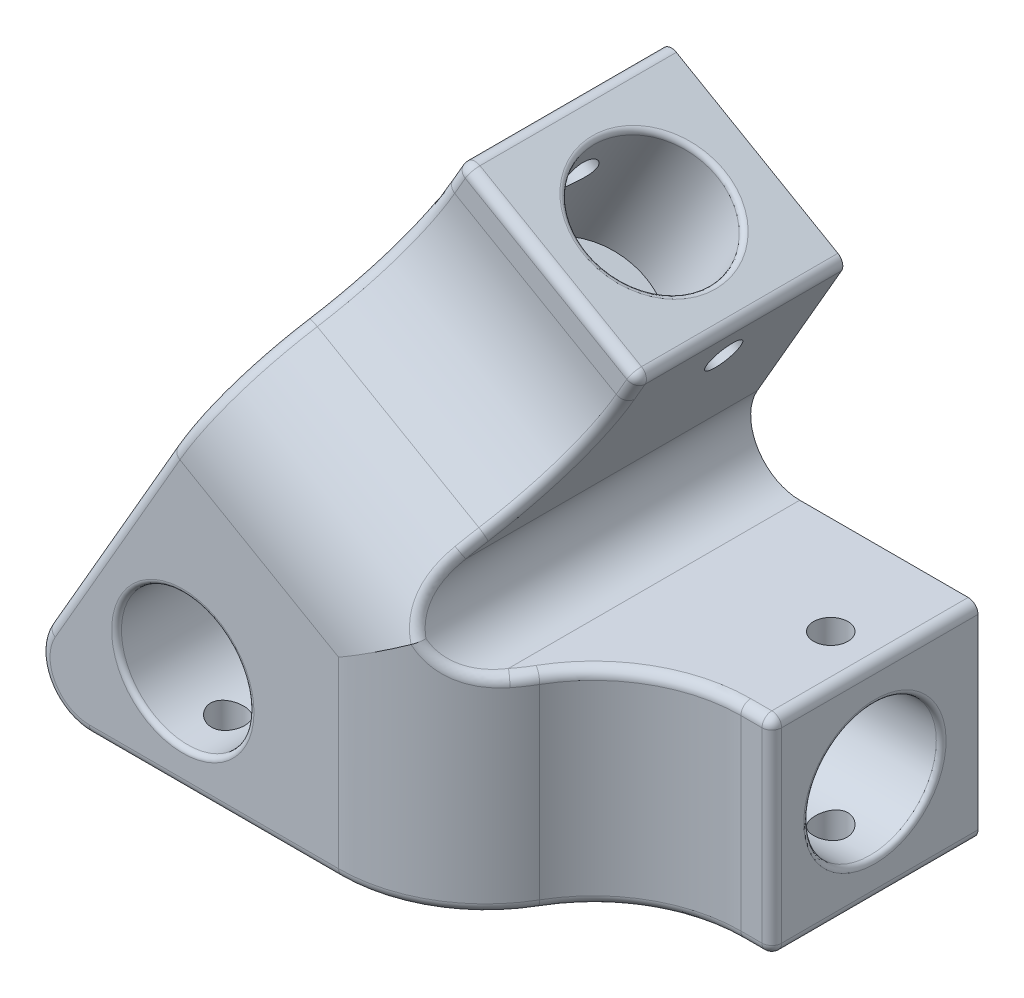
SolidWorks part; units mm, degrees
other "Corner Joint"
ref_plane "Front Plane" through (0, 0, 0) normal (0, 0, 1) x (1, 0, 0)
ref_plane "Top Plane" through (0, 0, 0) normal (0, 1, 0) x (1, 0, 0)
ref_plane "Right Plane" through (0, 0, 0) normal (1, 0, 0) x (0, 0, -1)
sketch "Sketch1" plane through (0, 0, 0) normal (0, 0, 1) x (1, 0, 0)
  line L0 (0, 0) -> (45, 0) construction
  line L1 (0, 0) -> (22.5, 38.9711) construction
  line L16 (45, -10.5) -> (-9.5263, -10.5)
  line L17 (16.8708, 42.2211) -> (28.1292, 35.7211) construction
  line L18 (16.8708, 42.2211) -> (9.3708, 29.2308) construction
  line L19 (9.3708, 29.2308) -> (20.6292, 22.7308) construction
  line L20 (28.1292, 35.7211) -> (20.6292, 22.7308) construction
  line L21 (30, 6.5) -> (45, 6.5) construction
  line L22 (30, 6.5) -> (30, -6.5) construction
  line L23 (30, -6.5) -> (45, -6.5) construction
  line L24 (45, 6.5) -> (45, -6.5) construction
  line L25 (-13.8564, -3) -> (13.4067, 44.2211)
  line L26 (13.4067, 44.2211) -> (31.5933, 33.7211)
  line L27 (31.5933, 33.7211) -> (22.5167, 18)
  line L28 (26.8468, 10.5) -> (45, 10.5)
  line L29 (45, 10.5) -> (45, -10.5)
  circle A0 centre (0, 0) radius 6.5 construction
  arc A1 (26.8468, 10.5) -> (22.5167, 18) centre (26.8468, 15.5) cw
  arc A2 (-9.5263, -10.5) -> (-13.8564, -3) centre (-9.5263, -5.5) cw
  point P2 (22.5, 38.9711)
  point P12 (45, 0)
  dimension "D7" = 15
  dimension "D8" = 13
  dimension "D13" = 5
  dimension "D1" = 60
  dimension "D2" = 45
  dimension "D3" = 45
  dimension "D4" = 13
  dimension "D5" = 15
  dimension "D6" = 13
  dimension "D9" = 4
  dimension "D10" = 4
  dimension "D11" = 4
  dimension "D12" = 4
extrude "Boss-Extrude3" add sketch "Sketch1" along normal blind 21
sketch "Sketch3" plane through (0, 0, 21) normal (0, 0, 1) x (1, 0, 0)
  line L0 (22.5167, 18) -> (4.3301, 28.5)
  line L1 (-13.8564, -3) -> (13.4067, 44.2211) construction
  line L2 (26.8468, 10.5) -> (26.8468, -10.5)
  line L3 (45, -10.5) -> (-9.5263, -10.5) construction
  line L4 (13.4067, 44.2211) -> (31.5933, 33.7211) construction
  line L5 (4.3301, 28.5) -> (-13.8564, -3)
  line L6 (-9.5263, -10.5) -> (26.8468, -10.5)
  line L7 (26.8468, 10.5) -> (26.6736, 10.5)
  line L8 (22.4301, 17.85) -> (22.5167, 18)
  line L9 (31.5933, 33.7211) -> (22.5167, 18) construction
  line L10 (26.8468, 10.5) -> (45, 10.5) construction
  circle A0 centre (0, 0) radius 6.75
  arc A1 (-9.5263, -10.5) -> (-13.8564, -3) centre (-9.5263, -5.5) cw
  arc A3 (22.5167, 18) -> (26.8468, 10.5) centre (26.8468, 15.5) ccw
  arc M12 (26.8468, 10.5) -> (22.5167, 18) centre (26.8468, 15.5) cw
  line M15 (13.4067, 44.2211) -> (-13.8564, -3)
  arc M16 (-13.8564, -3) -> (-9.5263, -10.5) centre (-9.5263, -5.5) ccw
  line M17 (-9.5263, -10.5) -> (45, -10.5)
  dimension "D1" = 5
  dimension "D2" = 13.5
extrude "Boss-Extrude4" add sketch "Sketch3" along normal blind 15 contours L2 L0 A0 M12 M15 M16 M17 region at (9.2242, 5.3256, 21)
sketch "Sketch4" plane through (45, 0, 0) normal (1, 0, 0) x (0, 0, -1)
  line L0 (-21, -10.5) -> (-21, 10.5) construction
  line L1 (-21, -10.5) -> (0, -10.5) construction
  circle A0 centre (-10.5, 0) radius 6.75
  dimension "D1" = 13.5
  dimension "D2" = 10.5
  dimension "D3" = 10.5
extrude "Cut-Extrude1" cut sketch "Sketch4" against normal blind 15
sketch "Sketch5" plane through (22.5, 38.9711, 0) normal (0.5, 0.866, 0) x (0.866, -0.5, 0)
  line L0 (-10.5, -21) -> (-10.5, 0) construction
  line L1 (10.5, 0) -> (-10.5, 0) construction
  circle A0 centre (0, -10.5) radius 6.75
  dimension "D1" = 13.5
  dimension "D2" = 10.5
  dimension "D3" = 10.5
extrude "Cut-Extrude2" cut sketch "Sketch5" against normal blind 15
fillet "Fillet1" radius 15 2 edges at (13.4234, 23.25, 21) (26.8468, 0, 21)
fillet "Fillet2" radius 15 2 edges at (26.8468, 0, 36) (13.4234, 23.25, 36)
fillet "Fillet3" radius 1 23 edges at (24.1108, 11.315, 33.5309) (27.9284, 10.5, 29.9162) (43.4234, 10.5, 21) (30.805, 32.3558, 21) (21.8979, 16.2133, 32.906) (23.0575, 18.9367, 29.9162) (43.4234, -10.5, 21) (34.3468, -10.5, 23.0096) (23.366, -10.5, 33.9904) (3.1699, -10.5, 36) (-13.8564, -8, 36) (-7.5083, 7.9952, 36) (2.5897, 25.4856, 33.9904) (12.6184, 42.8558, 21) (45, -10.5, 10.5) (45, 10.5, 10.5) (45, 0, 21) (34.3468, 10.5, 23.0096) (31.5933, 33.7211, 10.5) (22.5, 38.9711, 21) (26.2667, 24.4952, 23.0096) (8.0801, 34.9952, 23.0096) (13.4067, 44.2211, 10.5)
fillet "Fillet4" radius 0.5 3 edges at (45, 6.75, 10.5) (16.6543, 42.3461, 10.5) (6.75, 0, 36)
sketch "Sketch6" plane through (0, -10.5, 0) normal (0, -1, 0) x (1, 0, 0)
  line L0 (-9.5263, 2) -> (44, 2) construction
  line L1 (-9.5263, 35) -> (-9.5263, 0) construction
  line L2 (44, 0) -> (44, 20) construction
  line L3 (-9.5263, 0) -> (44, 0) construction
  text T0 " V2.0" font "Georgia" height in points 18
  dimension "D1" = 2
extrude "Cut-Extrude3" cut sketch "Sketch6" against normal blind 0.5
sketch "Sketch7" plane through (0, -10.5, 0) normal (0, -1, 0) x (1, 0, 0)
  line L0 (45, 20) -> (45, 0) construction
  line L1 (-9.5263, 36) -> (15.866, 36) construction
  circle A0 centre (40, 10) radius 1.75
  circle A1 centre (-0.4147, 31) radius 1.75
  point P4 (45, 10)
  dimension "D1" = 3.5
  dimension "D2" = 5
  dimension "D3" = 5
extrude "Cut-Extrude4" cut sketch "Sketch7" against normal blind 22
sketch "Sketch8" plane through (-9.0933, 5.25, 0) normal (-0.866, 0.5, 0) x (0, 0, 1)
  line L0 (0, 45) -> (20, 45) construction
  circle A0 centre (10, 40) radius 1.75
  point P5 (10, 45)
  dimension "D1" = 3.5
  dimension "D2" = 5
extrude "Cut-Extrude5" cut sketch "Sketch8" against normal blind 24
